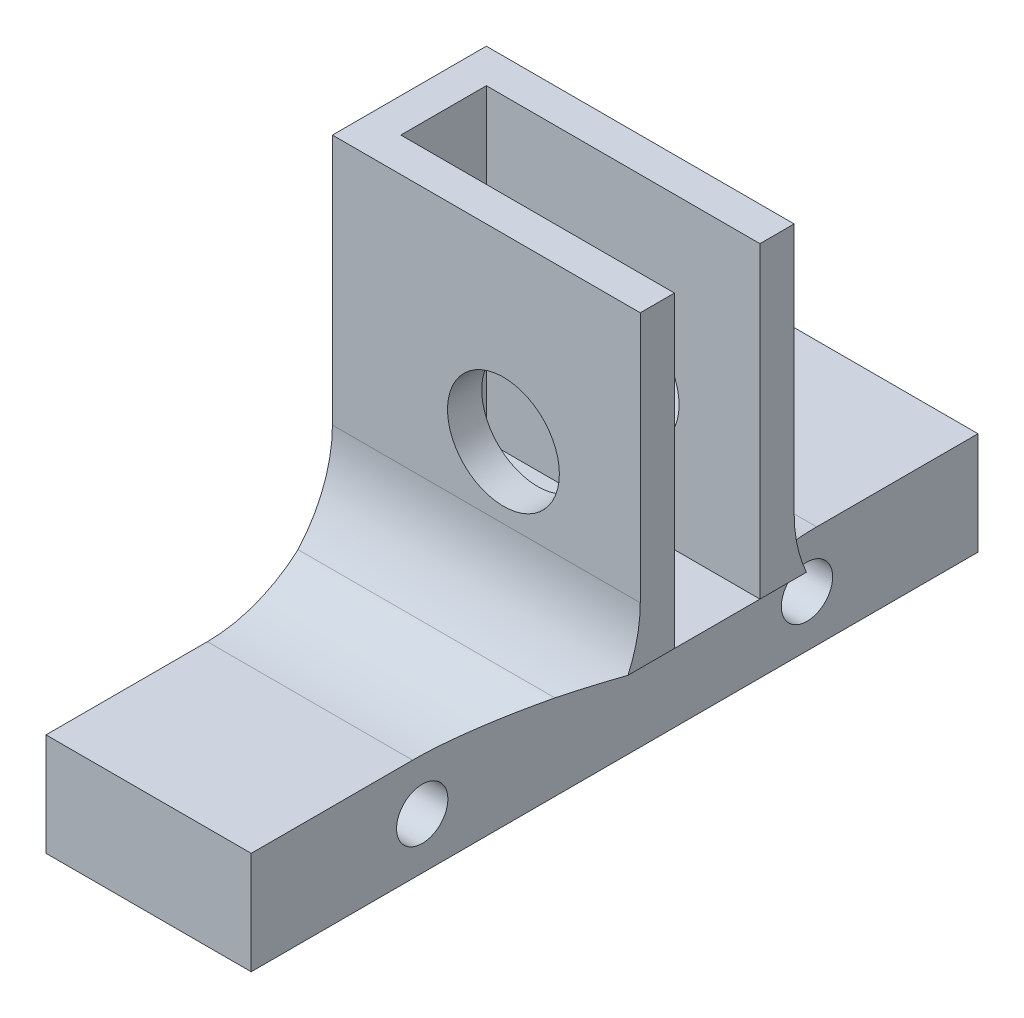
SolidWorks part; units mm, degrees
ref_plane "Plan de face" through (0, 0, 0) normal (0, 0, 1) x (1, 0, 0)
ref_plane "Plan de dessus" through (0, 0, 0) normal (0, 1, 0) x (1, 0, 0)
ref_plane "Plan de droite" through (0, 0, 0) normal (1, 0, 0) x (0, 0, -1)
sketch "Esquisse1" plane through (0, 0, 0) normal (0, 0, -1) x (1, 0, 0)
  line L0 (-1.3845, -46.2204) -> (38.6155, -46.2204)
  line L1 (38.6155, -46.2204) -> (38.6155, -42.2204)
  line L2 (38.6155, -42.2204) -> (24.6155, -42.2204)
  line L3 (24.6155, -42.2204) -> (24.6155, -36.2204)
  line L4 (24.6155, -36.2204) -> (12.6155, -36.2204)
  line L5 (12.6155, -36.2204) -> (12.6155, -42.2204)
  line L6 (12.6155, -42.2204) -> (-1.3845, -42.2204)
  line L7 (-1.3845, -42.2204) -> (-1.3845, -46.2204)
  dimension "D1" = 14
  dimension "D2" = 4
  dimension "D3" = 14
  dimension "D4" = 6
  dimension "D5" = 12
  dimension "D6" = 6
extrude "Boss.-Extru.1" add sketch "Esquisse1" along normal blind 42.5
hole_wizard "Dégagement M31" positions "Esquisse4" profile "Esquisse5" hole size "M3" standard "Din" end condition through all
sketch "Esquisse4" plane through (24.6155, 0, 0) normal (1, 0, 0) x (0, 0, -1)
  line L0 (0, 39.2204) -> (42.5, 39.2204) construction
  line L1 (0, 42.2204) -> (0, 36.2204) construction
  line L2 (42.5, 42.2204) -> (42.5, 36.2204) construction
  point P0 (10, 39.2204)
  point P2 (32.5, 39.2204)
  dimension "D1" = 10
  dimension "D2" = 10
sketch "Esquisse5" plane through (24.6155, 39.2204, -10) normal (0, 1, 0) x (0, 0, -1)
  line L0 (0, 0) -> (0, 26)
  line L1 (0, 26) -> (1.5, 26)
  line L2 (1.5, 26) -> (1.5, 0)
  line L5 (1.5, 0) -> (0, 0)
  line L11 (0, -6.35) -> (0, 107.95) construction
  dimension "Diamètre du perçage jusqu'au prochain" = 3
  dimension "Profondeur du perçage jusqu'au prochain" = 26
sketch "Esquisse6" plane through (0, 46.2204, 0) normal (0, 1, 0) x (1, 0, 0)
  line L0 (14.6155, 21.25) -> (-1.3845, 21.25) construction
  line L1 (30.6155, 23.75) -> (14.6155, 23.75)
  line L2 (30.6155, 23.75) -> (30.6155, 25.75)
  line L3 (30.6155, 18.75) -> (14.6155, 18.75)
  line L4 (14.6155, 23.75) -> (14.6155, 18.75)
  line L5 (-1.3845, 42.5) -> (-1.3845, 0) construction
  line L6 (12.6155, 42.5) -> (12.6155, 0) construction
  line L8 (30.6155, 16.75) -> (12.6155, 16.75)
  line L9 (12.6155, 25.75) -> (12.6155, 16.75)
  line L10 (30.6155, 25.75) -> (12.6155, 25.75)
  line L11 (30.6155, 18.75) -> (30.6155, 16.75)
  line L12 (30.6155, 23.75) -> (30.6155, 18.75) construction
  line L14 (32.6155, 25.75) -> (12.6155, 25.75) construction
  line L15 (32.6155, 16.75) -> (12.6155, 16.75) construction
  line L16 (32.6155, 25.75) -> (32.6155, 16.75) construction
  dimension "D1" = 16
  dimension "D2" = 5
  dimension "D3" = 2
extrude "Boss.-Extru.2" add sketch "Esquisse6" along normal blind 18
sketch "Esquisse7" plane through (0, 0, -16.75) normal (0, 0, 1) x (1, 0, 0)
  line L1 (22.6155, 50.4204) -> (30.6155, 50.4204) construction
  line L3 (12.6155, 46.2204) -> (30.6155, 46.2204) construction
  line L5 (30.6155, 64.2204) -> (30.6155, 46.2204) construction
  circle A0 centre (22.6155, 53.6904) radius 3.27
  dimension "D1" = 6.54
  dimension "D2" = 4.2
extrude "Enlèv. mat.-Extru.1" cut sketch "Esquisse7" against normal through all
sketch "Esquisse8" plane through (0, 0, 0) normal (0, 0, 1) x (1, 0, 0)
  line L0 (30.6155, 46.2204) -> (24.6155, 42.2204)
  line L1 (24.6155, 42.2204) -> (24.6155, 36.2204)
  line L2 (24.6155, 36.2204) -> (12.6155, 36.2204)
  line L3 (12.6155, 36.2204) -> (12.6155, 42.2204)
  line L4 (12.6155, 42.2204) -> (12.6155, 46.2204)
  line L5 (12.6155, 46.2204) -> (-1.3845, 46.2204)
  line L6 (-1.3845, 42.2204) -> (-1.3845, 46.2204) construction
  line L7 (-1.3845, 46.2204) -> (38.6155, 46.2204) construction
  line L8 (-1.3845, 46.2204) -> (-1.3845, 34.1294)
  line L9 (-1.3845, 34.1294) -> (38.6155, 34.1294)
  line L10 (38.6155, 34.1294) -> (38.6155, 46.2204)
  line L11 (38.6155, 46.2204) -> (30.6155, 46.2204)
extrude "Enlèv. mat.-Extru.2" cut sketch "Esquisse8" against normal through all
sketch "Esquisse9" plane through (24.6155, 0, 0) normal (1, 0, 0) x (0, 0, -1)
  line L0 (16.75, 46.2204) -> (12.75, 42.2204)
  line L2 (12.75, 42.2204) -> (0, 42.2204)
  line L3 (0, 42.2204) -> (0, 46.2204)
  line L4 (0, 46.2204) -> (16.75, 46.2204)
  line L5 (25.75, 46.2204) -> (29.75, 42.2204)
  line L6 (29.75, 42.2204) -> (42.5, 42.2204)
  line L7 (42.5, 42.2204) -> (42.5, 46.2204)
  line L10 (42.5, 46.2204) -> (25.75, 46.2204)
  line L12 (42.5, 46.2204) -> (25.75, 46.2204) construction
  line L13 (42.5, 42.2204) -> (0, 42.2204) construction
  line L14 (42.5, 46.2204) -> (42.5, 42.2204) construction
  dimension "D1" = 45
extrude "Enlèv. mat.-Extru.3" cut sketch "Esquisse9" against normal through all and the other way through all
fillet "Congé4" radius 8 4 edges at (18.6155, 42.2204, -12.75) (21.6155, 46.2204, -16.75) (21.6155, 46.2204, -25.75) (18.6155, 42.2204, -29.75)
